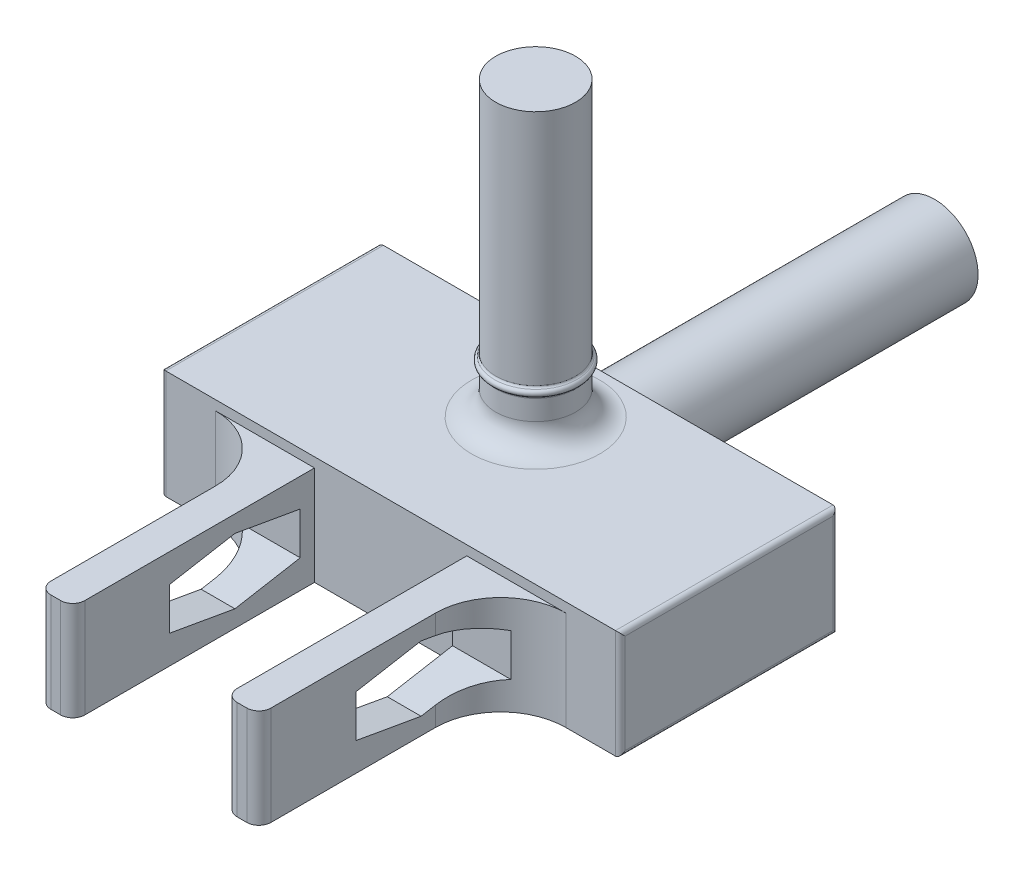
SolidWorks part; units mm, degrees
ref_plane "Front Plane" through (0, 0, 0) normal (0, 0, 1) x (1, 0, 0)
ref_plane "Top Plane" through (0, 0, 0) normal (0, 1, 0) x (1, 0, 0)
ref_plane "Right Plane" through (0, 0, 0) normal (1, 0, 0) x (0, 0, -1)
sketch "Szkic1" plane through (0, 0, 0) normal (0, 1, 0) x (1, 0, 0)
  line L0 (0, -13.1707) -> (0, 4.5) construction
  line L1 (4.55, -4.5) -> (-4.55, -4.5)
  line L2 (9.5, -4.5) -> (9.5, 4.5)
  line L3 (9.5, 4.5) -> (-9.5, 4.5)
  line L4 (-9.5, -4.5) -> (-9.5, 4.5)
  line L5 (9.5, -4.5) -> (-9.5, 4.5) construction
  line L6 (9.5, 4.5) -> (-9.5, -4.5) construction
  line L7 (-9.5, -4.5) -> (-4.55, -4.5)
  line L10 (2.5793, 4.5) -> (-2.5793, 4.5)
  line L13 (-4.55, -4.5) -> (-7.25, -4.5)
  line L14 (-4.55, -4.5) -> (-3.15, -4.5)
  line L15 (-4.55, -4.5) -> (-4.55, -14.5)
  line L16 (-4.55, -14.5) -> (-3.15, -14.5)
  line L17 (-3.15, -4.5) -> (-3.15, -14.5)
  line L18 (4.55, -4.5) -> (3.15, -4.5)
  line L19 (4.55, -4.5) -> (4.55, -14.5)
  line L20 (4.55, -14.5) -> (3.15, -14.5)
  line L21 (3.15, -4.5) -> (3.15, -14.5)
  line L22 (4.55, -4.5) -> (9.5, -4.5)
  line L23 (-4.55, -4.5) -> (-4.55, -7.2)
  line L26 (4.55, -4.5) -> (7.25, -4.5)
  line L27 (4.55, -4.5) -> (4.55, -7.2)
  arc A0 (-4.55, -7.2) -> (-7.25, -4.5) centre (-7.25, -7.2) ccw
  arc A1 (7.25, -4.5) -> (4.55, -7.2) centre (7.25, -7.2) ccw
  point P0 (0, 0)
  dimension "D1" = 9
  dimension "D2" = 19
  dimension "D3" = 10
  dimension "D4" = 1.4
  dimension "D5" = 6.3
  dimension "D6" = 2.7
extrude "Dodanie-wyciągnięcie1" add sketch "Szkic1" along normal blind 4.5 contours L1 L22 L2 L3 L4 L7 region at (0, 0, 0)
extrude "Dodanie-wyciągnięcie2" add sketch "Szkic1<7>" along normal blind 4.1 contours A0 L15 L7 | L17 L1 L15 L16 | A1 L22 L19 | L1 L21 L20 L19 region at (3.85, 0, 9.5) region at (5.1531, 0, 5.1031) region at (-3.85, 0, 9.5) region at (-5.1531, 0, 5.1031)
sketch "Szkic1<7>" plane through (0, 0, 0) normal (0, 1, 0) x (1, 0, 0) same geometry as "Szkic1"
ref_plane "Płaszczyzna1" through (0, 0, -4.5) normal (0, 0, -1) x (-1, 0, 0)
sketch "Szkic2" plane through (0, 0, -4.5) normal (0, 0, -1) x (-1, 0, 0)
  line L0 (0, 0) -> (0, 4.5) construction
  line L1 (-9.5, 4.5) -> (9.5, 4.5) construction
  circle A0 centre (0, 2.25) radius 1.8
  point P5 (0, 2.25)
  dimension "D1" = 3.6
extrude "Dodanie-wyciągnięcie3" add sketch "Szkic2" along normal blind 13.5
ref_plane "Płaszczyzna2" through (-3.15, 0, 0) normal (1, 0, 0) x (0, 0, -1)
sketch "Szkic3" plane through (-3.15, 0, 0) normal (1, 0, 0) x (0, 0, -1)
  line L0 (-7.79, 3.4) -> (-10.49, 2.9239)
  line L1 (-10.49, 2.9239) -> (-10.49, 1.1761)
  line L2 (-10.49, 1.1761) -> (-7.79, 0.7)
  line L3 (-7.79, 0.7) -> (-5.09, 1.1761)
  line L4 (-5.09, 1.1761) -> (-5.09, 2.9239)
  line L5 (-5.09, 2.9239) -> (-7.79, 3.4)
  line L7 (-4.5, 4.1) -> (-14.5, 4.1) construction
  line L8 (-4.5, 0) -> (-14.5, 0) construction
  point P10 (-10.89, 1.6482)
  point P11 (-10.49, 1.5761)
  dimension "D1" = 0.7
  dimension "D2" = 0.7
  dimension "D3" = 100
  dimension "D4" = 100
  dimension "D5" = 5.4
extrude "Wytnij-wyciągnięcie2" cut sketch "Szkic3" along normal through all both and the other way through all
fillet "Zaokrąglenie1" radius 0.5 4 edges at (3.15, 2.05, 14.5) (4.55, 2.05, 14.5) (-4.55, 2.05, 14.5) (-3.15, 2.05, 14.5)
fillet "Zaokrąglenie2" radius 0.2 8 edges at (-9.5, 2.25, -4.5) (-9.5, 4.5, 0) (9.5, 0, 0) (-9.5, 2.25, 4.5) (9.5, 2.25, 4.5) (9.5, 2.25, -4.5) (9.5, 4.5, 0) (-9.5, 0, 0)
ref_plane "Płaszczyzna3" through (0, 4.5, 0) normal (0, 1, 0) x (1, 0, 0)
sketch "Szkic4" plane through (0, 4.5, 0) normal (0, 1, 0) x (1, 0, 0)
  line L0 (-9.3, 1.5) -> (9.3, 1.5) construction
  line L1 (2.475, 4.5) -> (-2.475, 4.5) construction
  line L3 (-9.3, 4.5) -> (-9.3, -4.5) construction
  line L4 (9.3, -4.5) -> (9.3, 4.5) construction
  circle A0 centre (0, 1.5) radius 1.65
  point P6 (0, 1.5)
  dimension "D1" = 3.3
  dimension "D2" = 3
extrude "Dodanie-wyciągnięcie4" add sketch "Szkic4" along normal blind 5.1
ref_plane "Płaszczyzna4" through (0, 9.6, 0) normal (0, 1, 0) x (1, 0, 0)
sketch "Szkic5" plane through (0, 9.6, 0) normal (0, 1, 0) x (1, 0, 0)
  line L0 (0, 3.15) -> (0, -0.15) construction
  circle A0 centre (0, 1.5) radius 1.65 construction
  circle A1 centre (0, 1.5) radius 1.65
  point P5 (0, 1.5)
  dimension "D1" = 3.3
extrude "Dodanie-wyciągnięcie5" add sketch "Szkic5" along normal blind 7
fillet "Zaokrąglenie4" radius 1 1 edges at (0, 4.5, 0.15)
ref_axis "Oś1" through (0, 16.6, -1.5) along (0, -1, 0)
ref_point "Punkt1"
ref_point "Punkt2"
ref_plane "Płaszczyzna5" through (0, 0, 0) normal (1, 0, 0) x (0, 0, -1)
sketch "Szkic6" plane through (0, 0, 0) normal (1, 0, 0) x (0, 0, -1)
  line L0 (-1.1268, 5.9) -> (6.3719, 5.9) construction
  line L1 (1.5, 16.6) -> (1.5, 5.5) construction
  circle A0 centre (-0.15, 6.5593) radius 0.15
  point P2 (1.5, 16.6)
  point P3 (-0.15, 5.9)
  point P9 (0, 0)
  point P10 (0, 0)
  dimension "D3" = 0.3
  dimension "D1" = 10.7
  dimension "D2" = 1.65
revolve "Obrót1" add sketch "Szkic6" angle 360 about axis through (0, 16.6, -1.5) along (0, -1, 0)
fillet "Zaokrąglenie6" radius 0.1 2 edges at (0, 6.7093, -3.15) (0, 6.4093, 0.15)
ref_plane "Płaszczyzna Dolnia" through (0, 0, 0) normal (0, -1, 0) x (-1, 0, 0)
